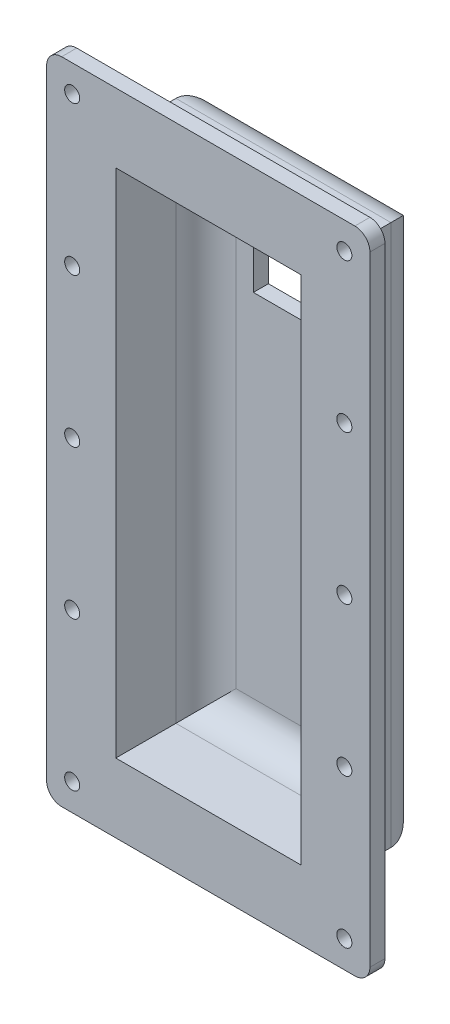
SolidWorks part; units mm, degrees
ref_plane "Front Plane" through (0, 0, 0) normal (0, 0, 1) x (1, 0, 0)
ref_plane "Top Plane" through (0, 0, 0) normal (0, 1, 0) x (1, 0, 0)
ref_plane "Right Plane" through (0, 0, 0) normal (1, 0, 0) x (0, 0, -1)
sketch "Sketch1" plane through (0, 0, 0) normal (0, 0, 1) x (1, 0, 0)
  line L1 (-17.88, 45) -> (17.88, 45)
  line L2 (-17.88, 45) -> (-17.88, -45)
  line L3 (-17.88, -45) -> (17.88, -45)
  line L4 (17.88, 45) -> (17.88, -45)
  line L5 (-17.88, 45) -> (17.88, -45) construction
  line L6 (-17.88, -45) -> (17.88, 45) construction
  point P0 (0, 0)
  dimension "D1" = 35.76
  dimension "D2" = 90
extrude "Boss-Extrude1" add sketch "Sketch1" along normal blind 15
sketch "Sketch2" plane through (0, 0, 15) normal (0, 0, 1) x (1, 0, 0)
  line L0 (-17.88, 45) -> (17.88, 45) construction
  line L1 (-26.88, 54) -> (26.88, 54)
  line L2 (-26.88, 54) -> (-26.88, -54)
  line L3 (-26.88, -54) -> (26.88, -54)
  line L4 (26.88, 54) -> (26.88, -54)
  line L5 (-26.88, 54) -> (26.88, -54) construction
  line L6 (-26.88, -54) -> (26.88, 54) construction
  line L7 (-17.88, 45) -> (-17.88, -45) construction
  point P0 (0, 0)
  point P8 (0, 45)
  dimension "D1" = 9
  dimension "D2" = 9
extrude "Boss-Extrude2" add sketch "Sketch2" along normal blind 2.5
shell "Shell1" thickness 2.5 removed face at (0, 0, 17.5)
fillet "Fillet1" radius 2.5 4 edges at (-26.88, -54, 16.25) (26.88, -54, 16.25) (26.88, 54, 16.25) (-26.88, 54, 16.25)
fillet "Fillet2" radius 5 8 edges at (0, -42.5, 2.5) (15.38, 0, 2.5) (-15.38, 0, 2.5) (0, 42.5, 2.5) (0, -45, 0) (17.88, 0, 0) (0, 45, 0) (-17.88, 0, 0)
sketch "Sketch3" plane through (0, 0, 2.5) normal (0, 0, 1) x (1, 0, 0)
  line L1 (-7.5, 29) -> (7.5, 29)
  line L2 (-7.5, 29) -> (-7.5, 21)
  line L3 (-7.5, 21) -> (7.5, 21)
  line L4 (7.5, 29) -> (7.5, 21)
  line L5 (-7.5, 29) -> (7.5, 21) construction
  line L6 (-7.5, 21) -> (7.5, 29) construction
  point P0 (0, 25)
  dimension "D1" = 8
  dimension "D2" = 15
  dimension "D3" = 25
extrude "Cut-Extrude1" cut sketch "Sketch3" against normal through all
sketch "Sketch4" plane through (0, 0, 17.5) normal (0, 0, 1) x (1, 0, 0)
  line L0 (17.88, 45) -> (17.88, -45) construction
  line L3 (-22.63, -49.5) -> (22.63, -49.5) construction
  line L10 (-22.63, -49.5) -> (-22.63, 49.5) construction
  line L11 (-22.63, 49.5) -> (22.63, 49.5) construction
  line L12 (22.63, -49.5) -> (22.63, 49.5) construction
  line L13 (-22.63, -49.5) -> (22.63, 49.5) construction
  line L14 (-22.63, 49.5) -> (22.63, -49.5) construction
  circle A16 centre (-22.63, 49.5) radius 1.25
  circle A17 centre (22.63, 49.5) radius 1.25
  circle A18 centre (22.63, 24.75) radius 1.25
  circle A19 centre (22.63, 0) radius 1.25
  circle A20 centre (22.63, -24.75) radius 1.25
  circle A21 centre (22.63, -49.5) radius 1.25
  circle A22 centre (-22.63, 24.75) radius 1.25
  circle A23 centre (-22.63, 0) radius 1.25
  circle A24 centre (-22.63, -24.75) radius 1.25
  circle A25 centre (-22.63, -49.5) radius 1.25
  point P0 (0, 0)
  dimension "D1" = 99
  dimension "D3" = 2.5
  dimension "D2" = 4.75
  dimension "D4" = 5
extrude "Cut-Extrude2" cut sketch "Sketch4" against normal up to surface (2.5 mm away) up to face at (0, 0, 15)
equation "\"case_width\"=35.76"
equation "\"D1@Sketch1\"=\"case_width\""
